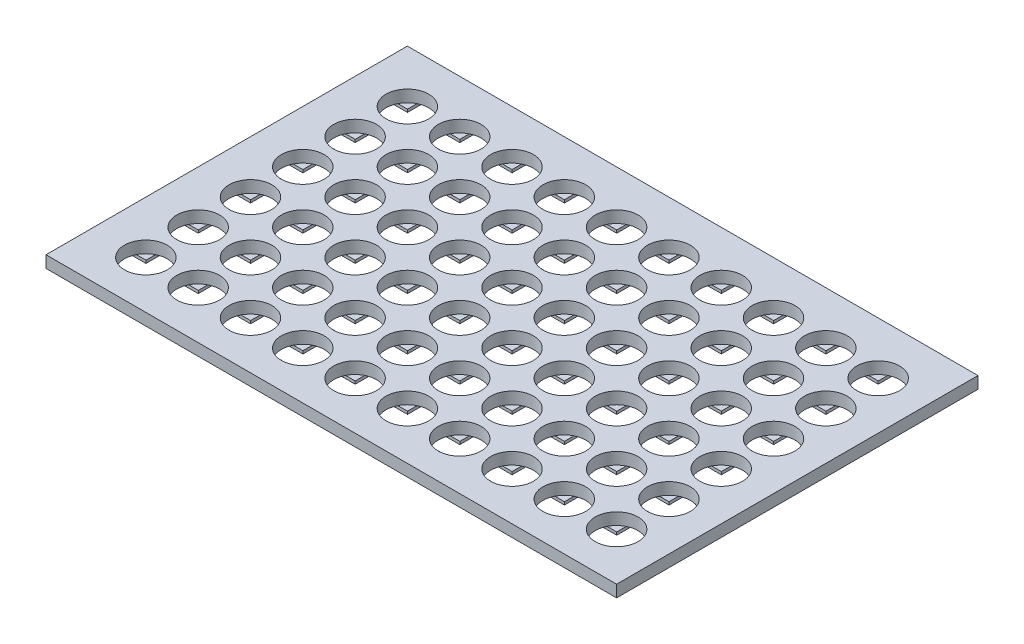
SolidWorks part; units mm, degrees
material "6061-T6 (SS)"
ref_plane "Front Plane" through (0, 0, 0) normal (0, 0, 1) x (1, 0, 0)
ref_plane "Top Plane" through (0, 0, 0) normal (0, 1, 0) x (1, 0, 0)
ref_plane "Right Plane" through (0, 0, 0) normal (1, 0, 0) x (0, 0, -1)
sketch "Sketch1" plane through (0, 0, 0) normal (0, 1, 0) x (1, 0, 0)
  line L1 (-120, 76) -> (120, 76)
  line L2 (-120, 76) -> (-120, -76)
  line L3 (-120, -76) -> (120, -76)
  line L4 (120, 76) -> (120, -76)
  line L5 (-120, 76) -> (120, -76) construction
  line L6 (-120, -76) -> (120, 76) construction
  point P0 (0, 0)
  dimension "D1" = 240
  dimension "D2" = 152
extrude "Boss-Extrude1" add sketch "Sketch1" along normal blind 5
sketch "Sketch2" plane through (0, 0, 0) normal (0, 1, 0) x (1, 0, 0)
  line L0 (-120, 76) -> (-120, -76) construction
  line L1 (120, 76) -> (-120, 76) construction
  circle A0 centre (-98, 54) radius 9
  circle A1 centre (-98, 32) radius 9
  circle A2 centre (-98, 10) radius 9
  circle A3 centre (-98, -12) radius 9
  circle A4 centre (-98, -34) radius 9
  circle A5 centre (-98, -56) radius 9
  circle A6 centre (-76, -12) radius 9
  circle A7 centre (-76, 10) radius 9
  circle A8 centre (-76, 32) radius 9
  circle A9 centre (-76, 54) radius 9
  circle A10 centre (-76, -34) radius 9
  circle A11 centre (-76, -56) radius 9
  circle A12 centre (-54, -12) radius 9
  circle A13 centre (-54, 10) radius 9
  circle A14 centre (-54, 32) radius 9
  circle A15 centre (-54, 54) radius 9
  circle A16 centre (-54, -34) radius 9
  circle A17 centre (-54, -56) radius 9
  circle A18 centre (-32, -12) radius 9
  circle A19 centre (-32, 10) radius 9
  circle A20 centre (-32, 32) radius 9
  circle A21 centre (-32, 54) radius 9
  circle A22 centre (-32, -34) radius 9
  circle A23 centre (-32, -56) radius 9
  circle A24 centre (-10, -12) radius 9
  circle A25 centre (-10, 10) radius 9
  circle A26 centre (-10, 32) radius 9
  circle A27 centre (-10, 54) radius 9
  circle A28 centre (-10, -34) radius 9
  circle A29 centre (-10, -56) radius 9
  circle A30 centre (12, -12) radius 9
  circle A31 centre (12, 10) radius 9
  circle A32 centre (12, 32) radius 9
  circle A33 centre (12, 54) radius 9
  circle A34 centre (12, -34) radius 9
  circle A35 centre (12, -56) radius 9
  circle A36 centre (34, -12) radius 9
  circle A37 centre (34, 10) radius 9
  circle A38 centre (34, 32) radius 9
  circle A39 centre (34, 54) radius 9
  circle A40 centre (34, -34) radius 9
  circle A41 centre (34, -56) radius 9
  circle A42 centre (56, -12) radius 9
  circle A43 centre (56, 10) radius 9
  circle A44 centre (56, 32) radius 9
  circle A45 centre (56, 54) radius 9
  circle A46 centre (56, -34) radius 9
  circle A47 centre (56, -56) radius 9
  circle A48 centre (78, -12) radius 9
  circle A49 centre (78, 10) radius 9
  circle A50 centre (78, 32) radius 9
  circle A51 centre (78, 54) radius 9
  circle A52 centre (78, -34) radius 9
  circle A53 centre (78, -56) radius 9
  circle A54 centre (100, -12) radius 9
  circle A55 centre (100, 10) radius 9
  circle A56 centre (100, 32) radius 9
  circle A57 centre (100, 54) radius 9
  circle A58 centre (100, -34) radius 9
  circle A59 centre (100, -56) radius 9
  dimension "D1" = 18
  dimension "D2" = 22
  dimension "D3" = 22
  dimension "D4" = 6
  dimension "D5" = 10
extrude "Cut-Extrude2" cut sketch "Sketch2" along normal blind 10
sketch "Sketch4" plane through (0, 0, 0) normal (0, 1, 0) x (1, 0, 0)
  line L0 (-98.0067, 63.0966) -> (-98.0067, 44.9995) construction
  line L1 (-107.0552, 54.0481) -> (-88.9581, 54.0481) construction
  line L2 (-107.0552, 50.0481) -> (-88.9581, 50.0481)
  line L3 (-107.0552, 58.0481) -> (-88.9581, 58.0481)
  line L4 (-102.0067, 63.0966) -> (-102.0067, 44.9995)
  line L5 (-94.0067, 63.0966) -> (-94.0067, 44.9995)
  line L6 (-107.0552, 58.0481) -> (-102.0067, 58.0481)
  line L7 (-102.0067, 58.0481) -> (-102.0067, 63.0966)
  line L8 (-107.0552, 50.0481) -> (-102.0067, 50.0481)
  line L9 (-102.0067, 50.0481) -> (-102.0067, 44.9995)
  line L10 (-94.0067, 44.9995) -> (-94.0067, 50.0481)
  line L11 (-94.0067, 50.0481) -> (-88.9581, 50.0481)
  line L12 (-88.9581, 58.0481) -> (-94.0067, 58.0481)
  line L13 (-94.0067, 58.0481) -> (-94.0067, 63.0966)
  line L15 (-102.0067, 58.0481) -> (-116.0067, 58.0481)
  line L16 (-102.0067, 58.0481) -> (-102.0067, 72.0481)
  line L17 (-102.0067, 72.0481) -> (-116.0067, 72.0481)
  line L18 (-116.0067, 58.0481) -> (-116.0067, 72.0481)
  arc A1 (-107.0552, 58.0481) -> (-102.0067, 63.0966) centre (-98.0067, 54.0481) ccw
  dimension "D5" = 14
  dimension "D6" = 14
  dimension "D1" = 4
  dimension "D2" = 4
  dimension "D3" = 4
  dimension "D4" = 4
extrude "Boss-Extrude5" add sketch "Sketch4" against normal blind 1.2 contours L18 L15 L3 L4 L16 L17 region at (-109.0067, 0, -65.0481)
pattern_linear "LPattern9" count 11 spacing 22 along (1, 0, 0) of "Boss-Extrude5"
pattern_linear "LPattern10" count 7 spacing 22 along (0, 0, 1) of "LPattern9"
